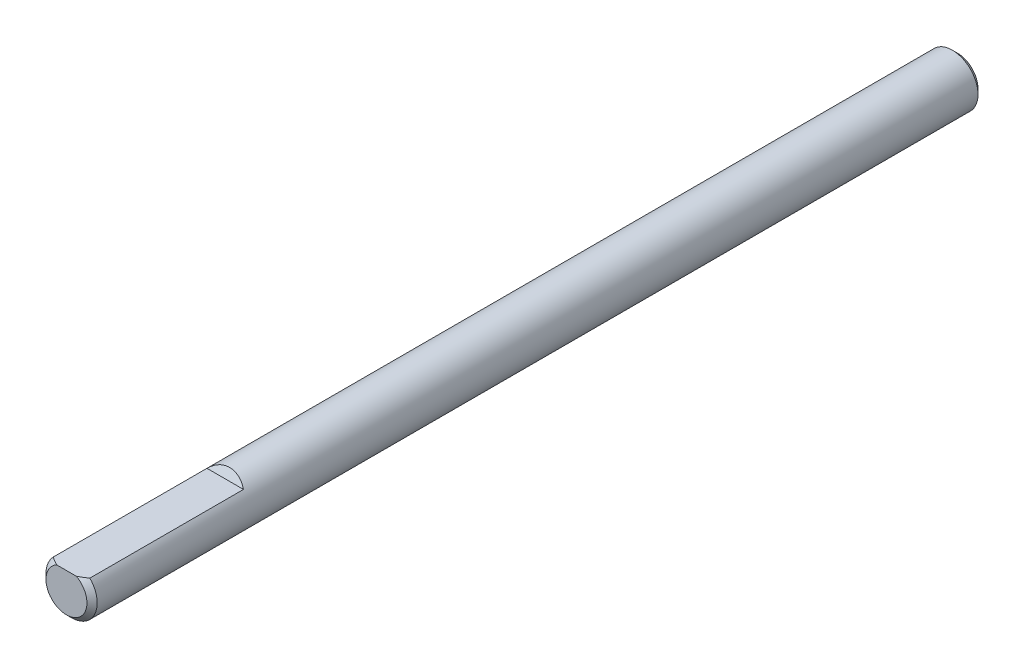
SolidWorks part; units mm, degrees
ref_plane "Front Plane" through (0, 0, 0) normal (0, 0, 1) x (1, 0, 0)
ref_plane "Top Plane" through (0, 0, 0) normal (0, 1, 0) x (1, 0, 0)
ref_plane "Right Plane" through (0, 0, 0) normal (1, 0, 0) x (0, 0, -1)
sketch "Sketch1" plane through (0, 0, 0) normal (0, 0, 1) x (1, 0, 0)
  circle A0 centre (0, 0) radius 2.5
  dimension "D1" = 5
extrude "Boss-Extrude1" add sketch "Sketch1" along normal blind 87
sketch "Sketch2" plane through (0, 0, 87) normal (0, 0, 1) x (1, 0, 0)
  line L1 (-2.5, -2.5) -> (2.5, -2.5) construction
  line L2 (-2.5, -2.5) -> (-2.5, 2.5) construction
  line L3 (-2.5, 2.5) -> (2.5, 2.5) construction
  line L4 (2.5, -2.5) -> (2.5, 2.5) construction
  line L5 (-2.5, -2.5) -> (2.5, 2.5) construction
  line L6 (-2.5, 2.5) -> (2.5, -2.5) construction
  line L7 (-2.5, 2.5) -> (2.5, 2.5)
  line L8 (-2.5, 2.5) -> (-2.5, 1.75)
  line L9 (-2.5, 1.75) -> (2.5, 1.75)
  line L10 (2.5, 2.5) -> (2.5, 1.75)
  circle A0 centre (0, 0) radius 2.5 construction
  point P0 (0, 0)
  dimension "D1" = 1.75
extrude "Cut-Extrude1" cut sketch "Sketch2" against normal blind 16
chamfer "Chamfer1" distance 0.5 angle 45 2 edges at (0, -2.5, 87) (2.5, 0, 0)
chamfer "Chamfer2" distance 0.5 angle 60 1 edges at (0, 1.75, 71) first distance on face at (-0.1362, 1.75, 81.5)
